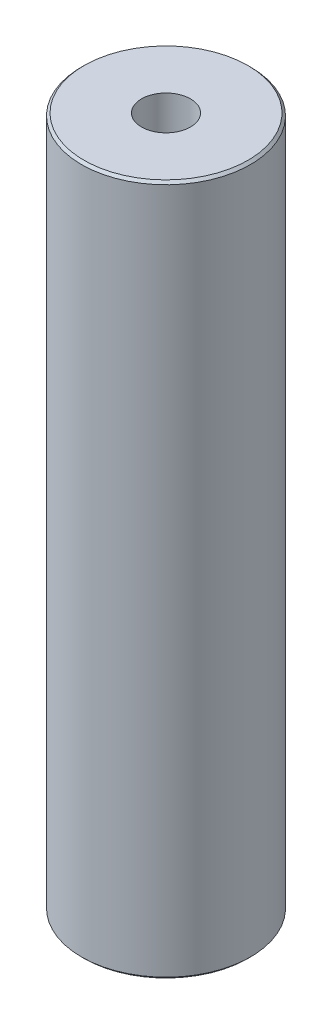
SolidWorks part; units mm, degrees
ref_plane "Front Plane" through (0, 0, 0) normal (0, 0, 1) x (1, 0, 0)
ref_plane "Top Plane" through (0, 0, 0) normal (0, 1, 0) x (1, 0, 0)
ref_plane "Right Plane" through (0, 0, 0) normal (1, 0, 0) x (0, 0, -1)
sketch "Sketch1" plane through (0, 0, 0) normal (0, 1, 0) x (1, 0, 0)
  circle A0 centre (0, 0) radius 27.5
  dimension "SHAFT_OD" = 55
extrude "Boss-Extrude1" add sketch "Sketch1" along normal blind 224.8962
sketch "Sketch2" plane through (0, 0, 0) normal (0, 1, 0) x (1, 0, 0)
  circle A0 centre (0, 0) radius 7.9572
  dimension "BORE_D" = 15.9144
extrude "Cut-Extrude1" cut sketch "Sketch2" along normal through all
chamfer "Chamfer1" distance 0.8074 angle 45 2 edges at (0, 224.8962, 27.5) (0, 0, 27.5)
